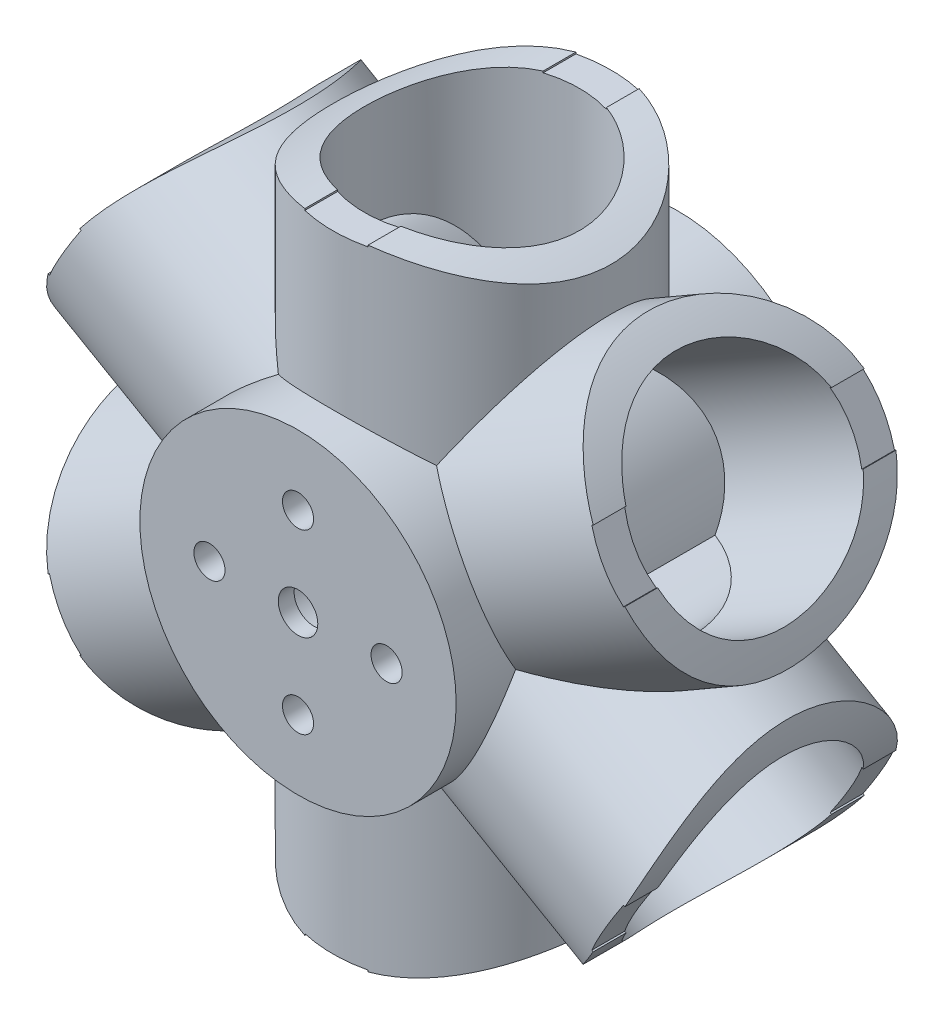
SolidWorks part; units mm, degrees
ref_plane "Front Plane" through (0, 0, 0) normal (0, 0, 1) x (1, 0, 0)
ref_plane "Top Plane" through (0, 0, 0) normal (0, 1, 0) x (1, 0, 0)
ref_plane "Right Plane" through (0, 0, 0) normal (1, 0, 0) x (0, 0, -1)
sketch "Sketch1" plane through (0, 0, 0) normal (0, 1, 0) x (1, 0, 0)
  circle A0 centre (0, 0) radius 11.176
  circle A1 centre (0, 0) radius 8.636
  dimension "D1" = 22.352
  dimension "D2" = 17.272
extrude "Boss-Extrude1" add sketch "Sketch1" along normal blind 20.32
sketch "Sketch2" plane through (0, 0, 0) normal (0, 0, 1) x (1, 0, 0)
  line L0 (11.176, 20.32) -> (-11.176, 20.32) construction
  line L1 (-8.636, 20.32) -> (-11.176, 20.32)
  line L2 (8.4632, 20.32) -> (11.0032, 20.32)
  line L3 (0, 20.32) -> (0, 38.4954) construction
  arc A2 (8.4632, 20.32) -> (-8.636, 20.32) centre (-0.0864, 7.6039) ccw
  arc A3 (11.0032, 20.32) -> (-11.176, 20.32) centre (-0.0864, 7.6039) ccw
revolve "Revolve1" add sketch "Sketch2" angle 360 about L3 region at (-9.906, 20.5457, 0)
ref_plane "Plane1" through (0, 27.94, 0) normal (0, -1, 0) x (-1, 0, 0)
sketch "Sketch3" plane through (0, 27.94, 0) normal (0, -1, 0) x (-1, 0, 0)
  line L0 (0, 11.9871) -> (0, -12.3331)
pattern_circular "CirPattern1" count 6 over 360 about axis through (0, 27.94, -11.9871) along (0, 0, 1) of bodies 103
sketch "Sketch4" plane through (0, 0, 0) normal (0, 0, 1) x (1, 0, 0)
  circle A0 centre (0, 27.94) radius 12.7
  dimension "D1" = 25.4
extrude "Boss-Extrude2" add sketch "Sketch4" along normal blind 13.97 and the other way blind 16.51
sketch "Sketch5" plane through (0, 0, 13.97) normal (0, 0, 1) x (1, 0, 0)
  circle A0 centre (0, 27.94) radius 25.4
  circle A1 centre (0, 27.94) radius 34.3456
  dimension "D1" = 50.8
extrude "Cut-Extrude1" cut sketch "Sketch5" against normal through all
sketch "Sketch8" plane through (0, 0, 0) normal (0, 1, 0) x (1, 0, 0)
  circle A0 centre (0, 0) radius 8.636
extrude "Cut-Extrude2" cut sketch "Sketch8" along normal up to surface (15.24 mm away) up to face at (0.2598, 15.3358, 2.1433)
pattern_circular "CirPattern2" count 6 over 360 about axis through (0, 27.94, -16.51) along (0, 0, 1) of "Cut-Extrude2"
sketch "Sketch9" plane through (0, 0, -16.51) normal (0, 0, -1) x (-1, 0, 0)
  line L0 (-159.3608, -65.013) -> (-26.0275, -65.013) construction
  line L1 (-5.3001, 25.0893) -> (-5.3001, 24.6378)
  line L2 (-5.3001, 32.5511) -> (5.1143, 32.5511)
  line L3 (-6.5701, 31.2811) -> (-6.5701, 23.7722)
  line L4 (-5.3001, 22.5022) -> (5.1143, 22.5022)
  line L5 (6.3843, 31.2811) -> (6.3843, 23.7722)
  line L6 (-4.9342, 31.6555) -> (4.7922, 31.6555)
  line L7 (-5.6962, 30.8935) -> (-5.6962, 24.1162)
  line L8 (-4.9342, 23.3542) -> (4.7922, 23.3542)
  line L9 (5.5542, 30.8935) -> (5.5542, 24.1162)
  line L10 (-5.3001, 24.6378) -> (-3.6843, 24.6378)
  line L11 (-3.6843, 24.6378) -> (-3.6843, 25.0893)
  line L12 (-3.6843, 25.0893) -> (-4.0153, 25.0893)
  line L13 (-4.0153, 25.0893) -> (-2.7662, 29.1074)
  line L14 (-2.7662, 29.1074) -> (-0.7496, 27.3015)
  line L15 (-0.7496, 27.3015) -> (-0.7496, 24.8635)
  line L16 (-0.7496, 24.8635) -> (-1.5021, 24.8635)
  line L17 (-1.5021, 24.8635) -> (-1.5021, 24.4572)
  line L18 (-1.5021, 24.4572) -> (-0.2379, 24.4572)
  line L19 (-0.2379, 24.4572) -> (-0.2379, 31.2811)
  line L20 (-0.2379, 31.2811) -> (-1.7579, 31.2811)
  line L21 (-1.7579, 31.2811) -> (-1.7579, 30.7478)
  line L22 (-1.7579, 30.7478) -> (-0.7496, 30.7478)
  line L23 (-0.7496, 30.7478) -> (-0.7496, 28.656)
  line L24 (-0.7496, 28.656) -> (-2.6007, 30.507)
  line L25 (-2.6007, 30.507) -> (-4.3163, 25.0893)
  line L26 (-4.3163, 25.0893) -> (-5.3001, 25.0893)
  line L27 (-0.071, 31.6555) -> (-0.071, 23.3542) construction
  line L28 (2.4587, 30.507) -> (4.1743, 25.0893)
  line L29 (0.6076, 28.656) -> (2.4587, 30.507)
  line L30 (0.6076, 30.7478) -> (0.6076, 28.656)
  line L31 (1.6159, 30.7478) -> (0.6076, 30.7478)
  line L32 (1.6159, 31.2811) -> (1.6159, 30.7478)
  line L33 (0.0959, 31.2811) -> (1.6159, 31.2811)
  line L34 (0.0959, 24.4572) -> (0.0959, 31.2811)
  line L35 (1.3601, 24.4572) -> (0.0959, 24.4572)
  line L36 (1.3601, 24.8635) -> (1.3601, 24.4572)
  line L37 (0.6076, 24.8635) -> (1.3601, 24.8635)
  line L38 (0.6076, 27.3015) -> (0.6076, 24.8635)
  line L39 (2.6242, 29.1074) -> (0.6076, 27.3015)
  line L40 (3.8733, 25.0893) -> (2.6242, 29.1074)
  line L41 (3.5422, 25.0893) -> (3.8733, 25.0893)
  line L42 (3.5422, 24.6378) -> (3.5422, 25.0893)
  line L43 (5.158, 24.6378) -> (3.5422, 24.6378)
  line L44 (5.158, 25.0893) -> (5.158, 24.6378)
  line L45 (4.1743, 25.0893) -> (5.158, 25.0893)
  line L47 (-5.3001, 24.3067) -> (5.1143, 24.3067)
  line L48 (-5.3001, 24.3067) -> (-5.3001, 23.8703)
  line L49 (-5.3001, 23.8703) -> (5.1143, 23.8703)
  line L50 (5.1143, 24.3067) -> (5.1143, 23.8703)
  arc A0 (5.1143, 32.5511) -> (6.3843, 31.2811) centre (5.1143, 31.2811) cw
  arc A1 (5.1143, 22.5022) -> (6.3843, 23.7722) centre (5.1143, 23.7722) ccw
  arc A2 (-6.5701, 23.7722) -> (-5.3001, 22.5022) centre (-5.3001, 23.7722) ccw
  arc A3 (-5.3001, 32.5511) -> (-6.5701, 31.2811) centre (-5.3001, 31.2811) ccw
  arc A4 (4.7922, 31.6555) -> (5.5542, 30.8935) centre (4.7922, 30.8935) cw
  arc A5 (4.7922, 23.3542) -> (5.5542, 24.1162) centre (4.7922, 24.1162) ccw
  arc A6 (-5.6962, 24.1162) -> (-4.9342, 23.3542) centre (-4.9342, 24.1162) ccw
  arc A7 (-4.9342, 31.6555) -> (-5.6962, 30.8935) centre (-4.9342, 30.8935) ccw
  dimension "D1" = 1.27
  dimension "D2" = 0.762
extrude "Cut-Extrude3" [suppressed] cut sketch "Sketch9" against normal blind 1.27 contours L25 L26 L1 L10 L11 L12 L13 L14 L15 L16 L17 L18 L19 L20 L21 L22 L23 L24 | L45 L28 L29 L30 L31 L32 L33 L34 L35 L36 L37 L38 L39 L40 L41 L42 L43 L44 | L2 A3 L3 A2 L4 A1 L5 A0 A7 L6 A4 L9 A5 L8 A6 L7
sketch "Sketch10" plane through (0, 0, 13.97) normal (0, 0, 1) x (1, 0, 0)
  circle A0 centre (0, 27.94) radius 1.5875
  arc A1 (-6.35, 38.9385) -> (-12.7, 27.94) centre (0, 27.94) ccw construction
  dimension "D1" = 3.175
extrude "Cut-Extrude4" cut sketch "Sketch10" against normal blind 1.27 contours A0
sketch "Sketch12" plane through (0, 0, 0) normal (0, 0, 1) x (1, 0, 0)
  line L1 (-12.7, 27.94) -> (-17.272, 27.94) construction
  arc A2 (-6.35, 38.9385) -> (-12.7, 27.94) centre (0, 27.94) ccw construction
  ellipse E0 centre (-12.7, 27.94) end of major axis (-17.78, 27.94) minor radius 1.27
  dimension "D1" = 10.16
  dimension "D2" = 2.54
extrude "Boss-Extrude3" add sketch "Sketch12" along normal up to next and the other way up to next
pattern_circular "CirPattern3" count 6 over 360 about axis through (0, 27.94, -16.51) along (0, 0, 1) of "Boss-Extrude3"
sketch "Sketch13" plane through (0, 0, -16.51) normal (0, 0, -1) x (-1, 0, 0)
  circle A0 centre (0, 27.94) radius 3.175
  circle A1 centre (0, 27.94) radius 12.7 construction
  dimension "D1" = 6.35
extrude "Cut-Extrude5" cut sketch "Sketch13" against normal up to surface (29.21 mm away) up to face at (1.5875, 27.94, 12.7)
sketch "Sketch14" plane through (0, 0, 13.97) normal (0, 0, 1) x (1, 0, 0)
  line L0 (-7.112, 27.94) -> (7.112, 27.94) construction
  circle A0 centre (-7.112, 27.94) radius 1.25
  circle A1 centre (7.112, 27.94) radius 1.25
  point P5 (0, 27.94)
  dimension "D1" = 2.5
  dimension "D2" = 14.224
extrude "Cut-Extrude6" cut sketch "Sketch14" against normal blind 7
pattern_circular "CirPattern4" count 2 over 90 about axis through (0, 27.94, 13.97) along (0, 0, 1) of "Cut-Extrude6"
sketch "Sketch15" plane through (0, 0, 13.97) normal (0, 0, 1) x (1, 0, 0)
  line L1 (-2.54, 56.7733) -> (2.54, 56.7733)
  line L2 (-2.54, 56.7733) -> (-2.54, 53.086)
  line L3 (-2.54, 53.086) -> (2.54, 53.086)
  line L4 (2.54, 56.7733) -> (2.54, 53.086)
  arc A0 (8.636, 51.8268) -> (-8.636, 51.8268) centre (0, 27.94) ccw construction
  point P4 (0, 53.34)
  point P5 (0, 56.7733)
  dimension "D1" = 0.254
  dimension "D2" = 5.08
extrude "Cut-Extrude7" cut sketch "Sketch15" against normal through all
pattern_circular "CirPattern5" count 6 over 360 about axis through (0, 27.94, 13.97) along (0, 0, 1) of "Cut-Extrude7"
